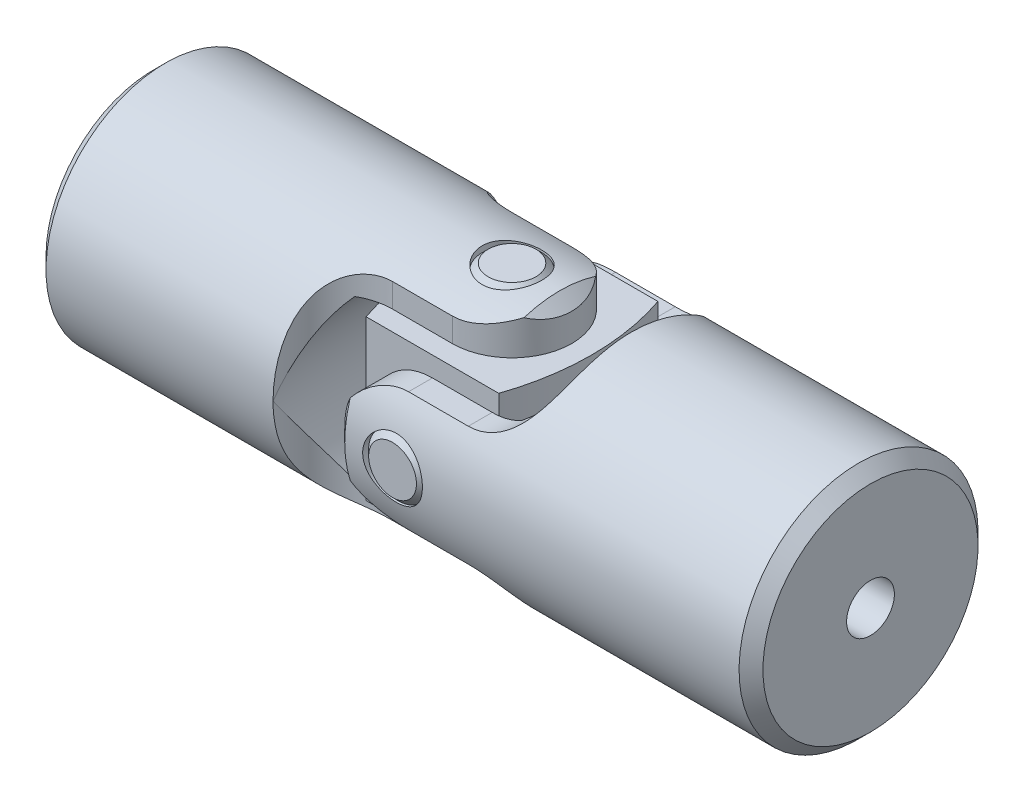
SolidWorks part; units mm, degrees
ref_plane "Front Plane" through (0, 0, 0) normal (0, 0, 1) x (1, 0, 0)
ref_plane "Top Plane" through (0, 0, 0) normal (0, 1, 0) x (1, 0, 0)
ref_plane "Right Plane" through (0, 0, 0) normal (1, 0, 0) x (0, 0, -1)
sketch "Sketch0" plane through (0, 0, 0) normal (0, 1, 0) x (1, 0, 0)
  line L0 (-47.625, 0) -> (47.625, 0) construction
  line L1 (-47.625, 15.875) -> (-47.625, -15.875) construction
  line L2 (-15.875, 3.175) -> (-15.875, -3.175) construction
  line L3 (-15.875, 3.175) -> (-12.7, 0) construction
  line L4 (-12.7, 0) -> (-15.875, -3.175) construction
  line L5 (-14.2875, 1.5875) -> (-14.2875, -1.5875) construction
  point P7 (-15.875, 0)
  point P8 (0, 0)
  point P12 (-14.2875, 0)
  dimension "D1" = 6.35
sketch "Sketch1" plane through (0, 0, 0) normal (0, 1, 0) x (1, 0, 0)
  line L0 (-47.625, 15.875) -> (-15.0813, 15.875)
  line L1 (7.9375, 15.875) -> (7.9375, 0)
  line L2 (7.9375, 0) -> (-47.625, 0)
  line L3 (-47.625, 0) -> (-47.625, 15.875)
  line L4 (-47.625, 15.875) -> (-47.625, -15.875) construction
  line L5 (-47.625, 0) -> (47.625, 0) construction
  line L6 (-15.0813, 15.875) -> (7.9375, 15.875)
  line L7 (-15.0813, 1.5875) -> (-15.0813, 15.875) construction
  line L11 (0, 0) -> (15.875, 0) construction
  line L12 (-14.2875, 1.5875) -> (-15.875, 1.5875) construction
  line L13 (-15.875, 3.175) -> (-15.875, -3.175) construction
  circle A0 centre (0, 0) radius 15.875 construction
  dimension "D3" = 55.5625
revolve "Revolve1" add sketch "Sketch1" angle 360 about L0
chamfer "Chamfer1" distance 1.5875 angle 45 2 edges at (-47.625, 0, 15.875) (7.9375, 0, 15.875)
sketch "Sketch2" plane through (0, 0, 0) normal (0, 1, 0) x (1, 0, 0)
  line L0 (-46.0375, 15.875) -> (-15.875, 15.875) construction
  line L1 (-15.0813, 15.875) -> (7.9375, 15.875) construction
  line L2 (6.35, 15.875) -> (-46.0375, 15.875) construction
  line L4 (-47.625, 0) -> (7.9375, 0) construction
  line L5 (-15.875, 15.875) -> (15.875, 15.875)
  line L6 (15.875, 15.875) -> (15.875, -15.875)
  line L7 (15.875, -15.875) -> (-15.875, -15.875)
  line L8 (0, 7.9375) -> (0, 0) construction
  line L9 (0, 7.9375) -> (-7.9375, 7.9375)
  line L10 (-15.875, 15.875) -> (-15.875, -15.875) construction
  line L11 (0, -7.9375) -> (-7.9375, -7.9375)
  arc A0 (-15.875, 15.875) -> (-7.9375, 7.9375) centre (-7.9375, 15.875) ccw
  arc A1 (0, -7.9375) -> (0, 7.9375) centre (0, 0) ccw
  arc A2 (-7.9375, -7.9375) -> (-15.875, -15.875) centre (-7.9375, -15.875) ccw
  dimension "D1" = 15.875
  dimension "D" = 31.75
extrude "Extrude1" cut sketch "Sketch2" against normal through all and the other way through all
sketch "Sketch3" plane through (0, 0, 0) normal (0, 0, 1) x (1, 0, 0)
  line L0 (-11.9062, 10.5728) -> (-15.875, 6.604) construction
  line L1 (-11.9062, 10.5728) -> (15.875, 10.5728)
  line L2 (-15.875, 6.604) -> (-15.875, -6.604) construction
  line L3 (-11.9062, -10.5728) -> (15.875, -10.5728)
  line L4 (15.875, 10.5728) -> (15.875, -10.5728)
  line L5 (-15.875, -6.604) -> (-11.9062, -10.5728) construction
  line L6 (-15.875, 0) -> (-7.9375, 0) construction
  line L7 (-7.9375, -13.7482) -> (-7.9375, 13.7482) construction
  line L8 (15.875, 0) -> (-15.875, 0) construction
  line L9 (-11.9062, 0) -> (-11.9062, 10.5728) construction
  arc A0 (-11.9062, 10.5728) -> (-11.9062, -10.5728) centre (0.1923, 0) ccw
  dimension "D1" = 21.1455
extrude "Extrude3" cut sketch "Sketch3" against normal through all and the other way through all
sketch "Sketch4" plane through (-47.625, 0, 0) normal (-1, 0, 0) x (0, 0, 1)
  circle A0 centre (0, 0) radius 3.175
  circle A1 centre (0, 0) radius 9.525 construction
  dimension "Max Bore Dia" = 19.05
extrude "Extrude4" cut sketch "Sketch4" against normal blind 6.35
sketch "Sketch5" plane through (-41.275, 0, 0) normal (-1, 0, 0) x (0, 0, 1)
  circle A0 centre (0, 0) radius 3.175 construction
  circle A1 centre (0, 0) radius 3.175
extrude "Extrude5" cut sketch "Sketch5" against normal through all draft 45
sketch "Sketch6" plane through (0, 0, 0) normal (0, 1, 0) x (1, 0, 0)
  line L0 (-47.625, 0) -> (47.625, 0) construction
  line L1 (7.9375, 0) -> (3.9687, 0) construction
  line L2 (3.9687, 0) -> (0, 0) construction
  circle A0 centre (0, 0) radius 3.9687
  arc A1 (0, -7.9375) -> (0, 7.9375) centre (0, 0) ccw construction
  dimension "D1" = 7.9375
extrude "Extrude6" cut sketch "Sketch6" against normal through all and the other way through all
mirror "Mirror1" about plane through (0, 0, 0) normal (1, 0, 0) of bodies 109 122
move or copy body "Body-Move/Copy1" bodies to move or copy 110 copy no rotation origin (0, 0, 0) rotation axis (1, 0, 0) rotation angle 90
sketch "Sketch18" plane through (0, 0, 0) normal (0, 1, 0) x (1, 0, 0)
  line L8 (0, 0) -> (47.625, 0) construction
  line L10 (-15.875, 3.175) -> (-47.625, 3.175)
  line L12 (-15.875, 3.175) -> (-15.875, -3.175)
  line L13 (-15.875, -3.175) -> (-47.625, -3.175)
  line L14 (-47.625, 15.875) -> (-47.625, -15.875) construction
  line L15 (0, 0) -> (0, 21.9558) construction
  line L16 (15.875, -3.175) -> (47.625, -3.175)
  line L17 (15.875, 3.175) -> (15.875, -3.175)
  line L18 (15.875, 3.175) -> (47.625, 3.175)
sketch "Sketch10" plane through (0, 0, 0) normal (0, 0, 1) x (1, 0, 0)
  line L0 (-10.5728, 10.5728) -> (10.5728, -10.5728) construction
  line L1 (-10.5728, 10.5728) -> (10.5728, 10.5728)
  line L2 (-10.5728, 10.5728) -> (-10.5728, -10.5728)
  line L3 (-10.5728, -10.5728) -> (10.5728, -10.5728)
  line L4 (10.5728, 10.5728) -> (10.5728, -10.5728)
  line L5 (0, 10.5728) -> (7.9375, 10.5728) construction
extrude "Extrude10" add sketch "Sketch10" against normal up to surface (10.5727 mm away) and the other way up to surface (10.5727 mm away) separate body up to face at (-3.9687, 0, -10.5728) other way up to face at (3.9688, 0, 10.5728)
sketch "Sketch20" plane through (0, 10.5728, 0) normal (0, 1, 0) x (1, 0, 0)
  line L4 (10.5728, 10.5727) -> (-10.5728, 10.5727) construction
  line L5 (10.5728, -10.5728) -> (-10.5728, -10.5728) construction
  line L6 (-10.5728, 10.5727) -> (-10.5728, -10.5728) construction
  line L7 (10.5728, 10.5727) -> (10.5728, -10.5728) construction
  line L8 (11.5888, -11.5888) -> (11.5888, 11.5887)
  line L9 (11.5888, 11.5887) -> (-11.5888, 11.5887)
  line L10 (-11.5888, 11.5887) -> (-11.5888, -11.5888)
  line L11 (-11.5888, -11.5888) -> (11.5888, -11.5888)
  line L12 (11.5888, -11.5888) -> (11.5888, 11.5887)
  line L13 (11.5888, 11.5887) -> (8.8106, 11.5887)
  line L14 (-11.5888, 11.5887) -> (-11.5888, -11.5888)
  line L15 (-11.5888, -11.5888) -> (-8.8106, -11.5888)
  line L16 (-8.8106, 10.5727) -> (-8.8106, 11.5887)
  line L17 (8.8106, 10.5727) -> (8.8106, 11.5887)
  line L18 (8.8106, -10.5728) -> (8.8106, -11.5888)
  line L19 (-8.8106, -10.5728) -> (-8.8106, -11.5888)
  line L20 (-8.8106, 11.5887) -> (-11.5888, 11.5887)
  line L21 (8.8106, -11.5888) -> (11.5888, -11.5888)
  line L22 (-47.625, 0) -> (7.9375, 0) construction
  line L23 (10.5728, 10.5727) -> (-10.5728, 10.5727) construction
  arc A0 (8.8106, 10.5727) -> (8.8106, -10.5728) centre (-22.0266, 0) cw
  arc A1 (-8.8106, 10.5727) -> (-8.8106, -10.5728) centre (22.0266, 0) ccw
  dimension "D2" = 21.1455
  dimension "D3" = 1.7621
  dimension "D1" = 1.016
extrude "Cut-Extrude2" cut sketch "Sketch20" against normal through all
sketch "Sketch13" plane through (0, 0, 0) normal (0, 1, 0) x (1, 0, 0)
  circle A0 centre (0, 0) radius 3.9687 construction
  circle A1 centre (0, 0) radius 3.9687
extrude "Extrude13" cut sketch "Sketch13" against normal through all and the other way through all
sketch "Sketch14" plane through (0, 0, 0) normal (0, 1, 0) x (1, 0, 0)
  circle A1 centre (0, 0) radius 3.9687
  circle A2 centre (0, 0) radius 3.9687
  dimension "D1" = 0
extrude "Extrude14" add sketch "Sketch14" along normal mid plane 31.75 separate body
sketch "Sketch15" plane through (0, 0, 0) normal (0, 0, 1) x (1, 0, 0)
  circle A0 centre (0, 0) radius 3.9687 construction
  circle A1 centre (0, 0) radius 3.9687
extrude "Extrude15" cut sketch "Sketch15" against normal through all and the other way through all
sketch "Sketch16" plane through (0, 0, 0) normal (0, 0, 1) x (1, 0, 0)
  circle A1 centre (0, 0) radius 3.9687
  circle A2 centre (0, 0) radius 3.9687
  dimension "D1" = 0
extrude "Extrude16" add sketch "Sketch16" along normal mid plane 31.75
chamfer "Chamfer3" distance 0.7937 angle 45 4 edges at (0, -15.875, 3.9687) (0, 15.875, 3.9687) (3.9688, 0, 15.875) (3.9688, 0, -15.875)
move or copy body "Body-Move/Copy2" [suppressed] bodies to move or copy 111 copy no rotation origin (0, 0, 0) rotation axis (0, 0, -1) rotation angle 35
equation "\"D2@Sketch3\" = \"D1@Sketch3\" / 4"
equation "\"D1@Extrude14\" = \"OD@Sketch0\""
equation "\"D1@Extrude16\" = \"D1@Extrude14\""
equation "\"D1@Sketch3\" = \"OD@Sketch0\"*.666"
equation "\"D1@Chamfer1\" = \"OD@Sketch0\"/20"
equation "\"D1@Chamfer3\" = \"D1@Chamfer1\"*.50"
equation "\"D3@Sketch20\" = \"D2@Sketch20\"/12"
